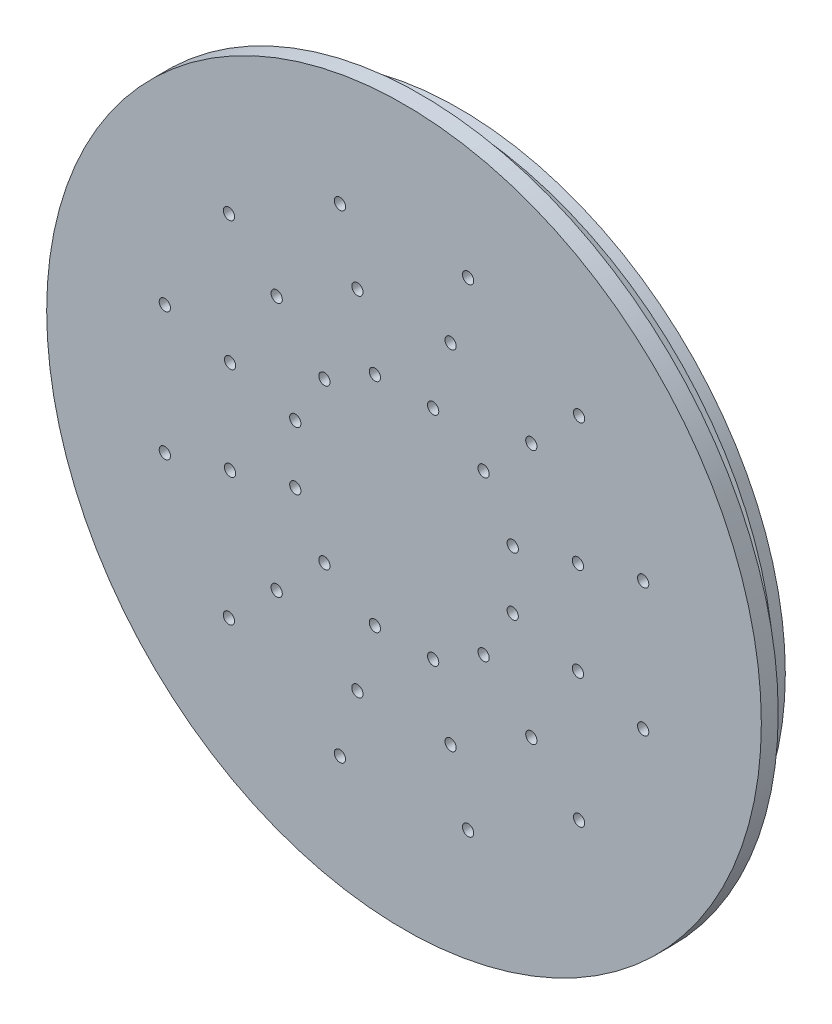
SolidWorks part; units mm, degrees
ref_plane "Front Plane" through (0, 0, 0) normal (1, 0, 0) x (0, 1, 0)
ref_plane "Top Plane" through (0, 0, 0) normal (0, 0, 1) x (0, 1, 0)
ref_plane "Right Plane" through (0, 0, 0) normal (0, 1, 0) x (-1, 0, 0)
sketch "Sketch1" plane through (0, 0, 0) normal (1, 0, 0) x (0, 1, 0)
  line L0 (0, 0) -> (58, 0)
  line L2 (53, 6.7625) -> (63.5, 6.7625)
  line L3 (63.5, 6.7625) -> (63.5, 9.7625)
  line L4 (63.5, 9.7625) -> (0, 9.7625)
  line L5 (0, 9.7625) -> (0, 0)
  line L6 (55, 0) -> (55, -14.3239) construction
  line L7 (58, 0) -> (58, 2)
  line L8 (58, 2) -> (53, 2)
  line L9 (53, 2) -> (53, 6.7625)
  line L10 (0, 4.3812) -> (53, 4.3812) construction
  line L11 (0, 6.7625) -> (53, 6.7625) construction
  circle A0 centre (0, 4.3812) radius 2.3812
  dimension "D1" = 63.5
  dimension "D2" = 3
  dimension "D3" = 4.7625
  dimension "D4" = 3
  dimension "D5" = 55
  dimension "D6" = 2
  dimension "D7" = 2
revolve "Revolve1" add sketch "Sketch1" angle 360 about L5 region at (0, 29.2584, 5.0124) region at (0, 1.0106, 4.3812)
extrude "Cut-Extrude1" cut sketch "Sketch1<3>" along normal through all from offset 5 contours L5 A0 | L5 A0 region at (0, -1.0106, 4.3812) region at (0, 1.0106, 4.3812)
sketch "Sketch1<3>" plane through (0, 0, 0) normal (1, 0, 0) x (0, 1, 0) same geometry as "Sketch1"
ref_plane "Plane1" through (0, 0, 4.3812) normal (0, 0, -1) x (0, 1, 0)
sketch "Sketch2" plane through (0, 0, 4.3812) normal (0, 0, 1) x (0, 1, 0)
  line L0 (0, 0) -> (0, -58) construction
  line L1 (0, 0) -> (31.75, -54.9926) construction
  line L2 (0, -54) -> (7.0484, -53.538) construction
  line L3 (7.0484, -53.538) -> (13.9762, -52.16) construction
  line L4 (13.9762, -52.16) -> (20.6649, -49.8895) construction
  line L5 (20.6649, -49.8895) -> (27, -46.7654) construction
  line L6 (0, 0) -> (16.435, -61.3363) construction
  line L7 (0, -45.5522) -> (22.7761, -39.4493) construction
  line L8 (0, -33.1288) -> (16.5644, -28.6904) construction
  line L9 (0, -20.7055) -> (10.3528, -17.9315) construction
  circle A0 centre (0, 0) radius 63.5 construction
  arc A1 (0, -54) -> (27, -46.7654) centre (0, 0) ccw construction
  circle A2 centre (0, 0) radius 63.5 construction
  circle A3 centre (11.388, -42.5007) radius 1
  circle A4 centre (8.2822, -30.9096) radius 1
  circle A6 centre (0, -54) radius 0.5
  circle A7 centre (13.9762, -52.16) radius 0.5
  circle A8 centre (7.0484, -53.538) radius 0.5
  circle A9 centre (20.6649, -49.8895) radius 0.5
  circle A10 centre (5.1764, -19.3185) radius 1
  circle A11 centre (0, 0) radius 58 construction
  dimension "D2" = 4
  dimension "D3" = 20
  dimension "D4" = 32
  dimension "D5" = 44
  dimension "D6" = 1
  dimension "D7" = 2
  dimension "D1" = 30
ref_plane "Plane2" through (42.5007, 11.388, 0) normal (0.9659, 0.2588, 0) x (-0.2588, 0.9659, 0)
ref_plane "Plane3" through (30.9096, 8.2822, 0) normal (0.9659, 0.2588, 0) x (-0.2588, 0.9659, 0)
ref_plane "Plane4" through (19.3185, 5.1764, 0) normal (0.9659, 0.2588, 0) x (-0.2588, 0.9659, 0)
sketch "Sketch4" plane through (42.5007, 11.388, 0) normal (0.9659, 0.2588, 0) x (-0.2588, 0.9659, 0)
  line L0 (-11.7898, 4.3812) -> (0, -28.0109)
  line L1 (0, -28.0109) -> (11.7898, 4.3812)
  line L2 (-11.7898, 4.3812) -> (-11.3199, 4.5523)
  line L3 (-11.3199, 4.5523) -> (0.4698, -27.8399)
  line L4 (0.4698, -27.8399) -> (0, -28.0109)
  line L5 (0, -28.0109) -> (-0.4698, -27.8399)
  line L6 (-0.4698, -27.8399) -> (11.3199, 4.5523)
  line L7 (11.3199, 4.5523) -> (11.7898, 4.3812)
  line L8 (-11.7898, 4.3812) -> (11.7898, 4.3812) construction
  dimension "D1" = 0.5
  dimension "D2" = 70
sketch "Sketch5" plane through (30.9096, 8.2822, 0) normal (0.9659, 0.2588, 0) x (-0.2588, 0.9659, 0)
  line L0 (-8.5744, 4.3812) -> (0, -19.1766)
  line L1 (-8.5744, 4.3812) -> (-8.1045, 4.5523)
  line L2 (0, -19.1766) -> (0.4698, -19.0056)
  line L3 (-8.1045, 4.5523) -> (0.4698, -19.0056)
  line L4 (8.5744, 4.3812) -> (0, -19.1766)
  line L5 (8.5744, 4.3812) -> (8.1045, 4.5523)
  line L6 (0, -19.1766) -> (-0.4698, -19.0056)
  line L7 (8.1045, 4.5523) -> (-0.4698, -19.0056)
  line L8 (-8.5744, 4.3812) -> (8.5744, 4.3812) construction
  dimension "D1" = 70
  dimension "D2" = 0.5
sketch "Sketch6" plane through (19.3185, 5.1764, 0) normal (0.9659, 0.2588, 0) x (-0.2588, 0.9659, 0)
  line L0 (-5.359, 4.3812) -> (0, -10.3424)
  line L1 (-5.359, 4.3812) -> (-4.8891, 4.5523)
  line L2 (0, -10.3424) -> (0.4698, -10.1714)
  line L3 (-4.8891, 4.5523) -> (0.4698, -10.1714)
  line L4 (0, -10.3424) -> (5.359, 4.3812)
  line L5 (0, -10.3424) -> (-0.4698, -10.1714)
  line L6 (5.359, 4.3812) -> (4.8891, 4.5523)
  line L7 (-0.4698, -10.1714) -> (4.8891, 4.5523)
  line L8 (-5.359, 4.3812) -> (5.359, 4.3812) construction
  dimension "D1" = 0.5
  dimension "D2" = 70
extrude "Cut-Extrude2" cut sketch "Sketch2" along normal up to next from surface contours A6 | A8 | A9 | A3 | A4 | A10 | A7 region at (42.5007, 11.388, 4.3812) region at (30.9096, 8.2822, 4.3812) region at (54, 0, 4.3812) region at (53.538, 7.0484, 4.3812) region at (49.8895, 20.6649, 4.3812) region at (19.3185, 5.1764, 4.3812) starting at face at (58, 0, 0)
revolve "Cut-Revolve1" cut sketch "Sketch4" angle 360 about L0 region at (44.0134, 5.7427, -11.2245)
revolve "Cut-Revolve2" cut sketch "Sketch4<3>" angle 360 about L1 region at (40.9881, 17.0334, -11.2245)
sketch "Sketch4<3>" plane through (42.5007, 11.388, 0) normal (0.9659, 0.2588, 0) x (-0.2588, 0.9659, 0) same geometry as "Sketch4"
revolve "Cut-Revolve3" cut sketch "Sketch5" angle 360 about L0 region at (32.0062, 4.1896, -6.8077)
revolve "Cut-Revolve4" cut sketch "Sketch5<3>" angle 360 about L4
sketch "Sketch5<3>" plane through (30.9096, 8.2822, 0) normal (0.9659, 0.2588, 0) x (-0.2588, 0.9659, 0) same geometry as "Sketch5"
revolve "Cut-Revolve5" cut sketch "Sketch6" angle 360 about L0 region at (19.9992, 2.6362, -2.3912)
revolve "Cut-Revolve6" cut sketch "Sketch6<4>" angle 360 about L4 region at (18.6379, 7.7166, -2.3912)
sketch "Sketch6<4>" plane through (19.3185, 5.1764, 0) normal (0.9659, 0.2588, 0) x (-0.2588, 0.9659, 0) same geometry as "Sketch6"
pattern_circular "CirPattern2" count 12 over 360 about axis through (0, 0, 9.7625) along (0, 0, 1) of "Cut-Extrude2", "Cut-Revolve1", "Cut-Revolve2", "Cut-Revolve3", "Cut-Revolve4", "Cut-Revolve5", "Cut-Revolve6", "Cut-Extrude1" reverse direction yes
